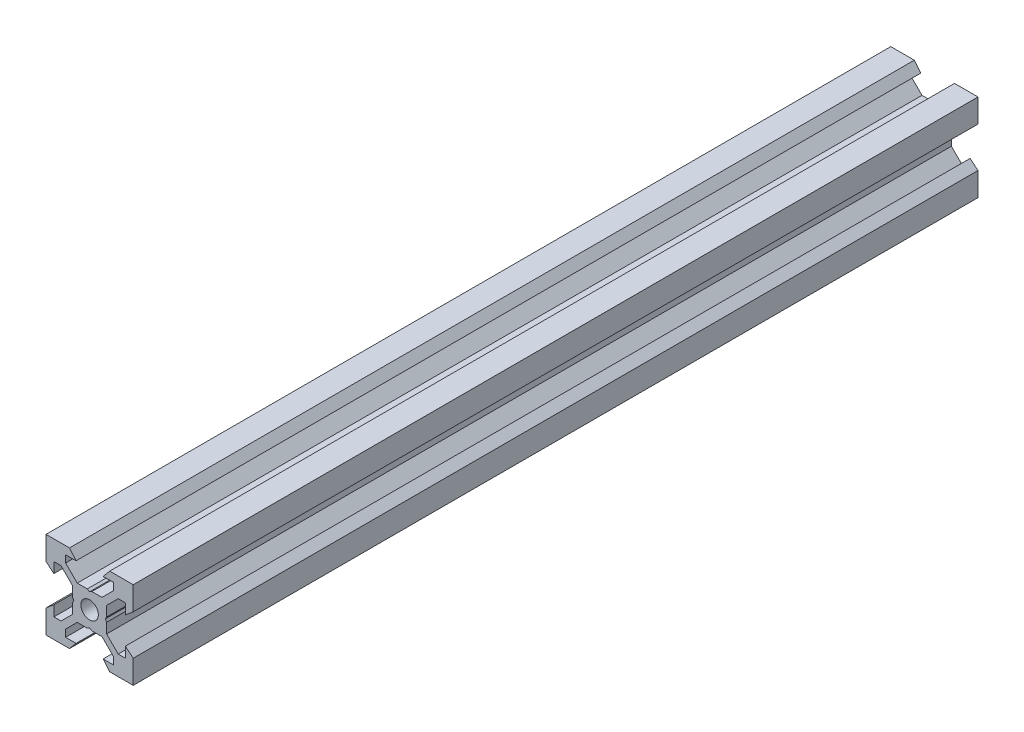
SolidWorks part; units mm, degrees
ref_plane "Front Plane" through (0, 0, 0) normal (0, 0, 1) x (1, 0, 0)
ref_plane "Top Plane" through (0, 0, 0) normal (0, 1, 0) x (1, 0, 0)
ref_plane "Right Plane" through (0, 0, 0) normal (1, 0, 0) x (0, 0, -1)
sketch "Sketch1" plane through (0, 0, 0) normal (0, 0, 1) x (1, 0, 0)
  line L0 (10, 10) -> (4.6104, 10) construction
  line L1 (10, 10) -> (10, 4.6104) construction
  line L2 (10, -10) -> (10, -4.6104) construction
  line L3 (10, -10) -> (4.6104, -10) construction
  line L4 (10, 10) -> (10, 4.6104)
  line L5 (6.5607, 5.5) -> (8.2, 5.5)
  line L6 (5.5, 8.2) -> (5.5, 6.5607)
  line L7 (10, 10) -> (4.6104, 10)
  line L8 (10, 10) -> (10, 4.6104)
  line L9 (6.5607, 5.5) -> (3.9, 2.8393)
  line L10 (5.5, 6.5607) -> (2.8393, 3.9)
  line L11 (10, 4.6104) -> (8.2, 3.1)
  line L12 (4.6104, 10) -> (3.1, 8.2)
  line L13 (8.2, 3.1) -> (8.2, 5.5)
  line L14 (3.1, 8.2) -> (5.5, 8.2)
  line L15 (-6.5607, 5.5) -> (-8.2, 5.5)
  line L16 (6.5607, -5.5) -> (8.2, -5.5)
  line L17 (3.1, -8.2) -> (5.5, -8.2)
  line L18 (8.2, -3.1) -> (8.2, -5.5)
  line L19 (4.6104, -10) -> (3.1, -8.2)
  line L20 (10, -4.6104) -> (8.2, -3.1)
  line L21 (0.5196, -3.9) -> (0, -3.6)
  line L22 (0.5196, 3.9) -> (0, 3.6)
  line L23 (3.6, 0) -> (3.9, -0.5196)
  line L24 (3.9, 0.5196) -> (3.6, 0)
  line L25 (3.9, 0.5196) -> (3.9, 2.8393)
  line L26 (2.8393, 3.9) -> (0.5196, 3.9)
  line L27 (3.9, -2.8393) -> (3.9, -0.5196)
  line L28 (2.8393, -3.9) -> (0.5196, -3.9)
  line L29 (5.5, -6.5607) -> (2.8393, -3.9)
  line L30 (6.5607, -5.5) -> (3.9, -2.8393)
  line L31 (10, -10) -> (10, -4.6104)
  line L32 (10, -10) -> (4.6104, -10)
  line L33 (5.5, -8.2) -> (5.5, -6.5607)
  line L34 (-6.5607, -5.5) -> (-8.2, -5.5)
  line L35 (10, -10) -> (10, -4.6104)
  line L36 (0, 0) -> (0, 8.2) construction
  line L37 (-10, -10) -> (-4.6104, -10) construction
  line L38 (-10, -10) -> (-10, -4.6104) construction
  line L39 (-10, 10) -> (-10, 4.6104) construction
  line L40 (-10, 10) -> (-4.6104, 10) construction
  line L41 (-10, -10) -> (-10, -4.6104)
  line L43 (-5.5, -8.2) -> (-5.5, -6.5607)
  line L44 (-10, -10) -> (-4.6104, -10)
  line L45 (-10, -10) -> (-10, -4.6104)
  line L46 (-6.5607, -5.5) -> (-3.9, -2.8393)
  line L47 (-5.5, -6.5607) -> (-2.8393, -3.9)
  line L48 (-2.8393, -3.9) -> (-0.5196, -3.9)
  line L49 (-3.9, -2.8393) -> (-3.9, -0.5196)
  line L50 (-2.8393, 3.9) -> (-0.5196, 3.9)
  line L51 (-3.9, 0.5196) -> (-3.9, 2.8393)
  line L52 (-3.9, 0.5196) -> (-3.6, 0)
  line L53 (-3.6, 0) -> (-3.9, -0.5196)
  line L54 (-0.5196, 3.9) -> (0, 3.6)
  line L55 (-0.5196, -3.9) -> (0, -3.6)
  line L56 (-10, -4.6104) -> (-8.2, -3.1)
  line L57 (-4.6104, -10) -> (-3.1, -8.2)
  line L58 (-8.2, -3.1) -> (-8.2, -5.5)
  line L59 (-3.1, -8.2) -> (-5.5, -8.2)
  line L60 (-10, -10) -> (10, -10) construction
  line L61 (-10, -10) -> (-10, 10) construction
  line L62 (-3.1, 8.2) -> (-5.5, 8.2)
  line L63 (-8.2, 3.1) -> (-8.2, 5.5)
  line L64 (-4.6104, 10) -> (-3.1, 8.2)
  line L65 (-10, 4.6104) -> (-8.2, 3.1)
  line L66 (-5.5, 6.5607) -> (-2.8393, 3.9)
  line L67 (-6.5607, 5.5) -> (-3.9, 2.8393)
  line L68 (-10, 10) -> (-10, 4.6104)
  line L69 (-10, 10) -> (-4.6104, 10)
  line L70 (-5.5, 8.2) -> (-5.5, 6.5607)
  line L71 (-10, 10) -> (10, 10) construction
  line L72 (-10, 10) -> (-10, 4.6104)
  line L73 (10, -10) -> (10, 10) construction
  line L74 (-10, -10) -> (10, 10) construction
  line L75 (-10, 10) -> (10, -10) construction
  circle A0 centre (0, 0) radius 2
  dimension "D7" = 4
  dimension "D1" = 20
  dimension "D2" = 5.3896
  dimension "D3" = 4.5
  dimension "D4" = 50
  dimension "D5" = 1.8
  dimension "D6" = 1.5104
  dimension "D8" = 5.5
  dimension "D9" = 120
  dimension "D10" = 0.3
  dimension "D11" = 2.3197
  dimension "D12" = 7.8
  dimension "D13" = 7.8
  dimension "D14" = 1.5
  dimension "D15" = 2.6607
extrude "Boss-Extrude1" add sketch "Sketch1" along normal mid plane 193.74 contours L70 L62 L64 L69 L68 L65 L63 L15 L67 L51 L52 L53 L49 L46 L34 L58 L56 L41 L44 L57 L59 L43 L47 L48 L55 L21 L28 L29 L33 L17 L19 L32 L31 L20 L18 L16 L30 L27 L23 L24 L25 L9 L5 L13 L11 L4 L7 L12 L14 L6 L10 region at (9.7172, 7.3052, 0)
